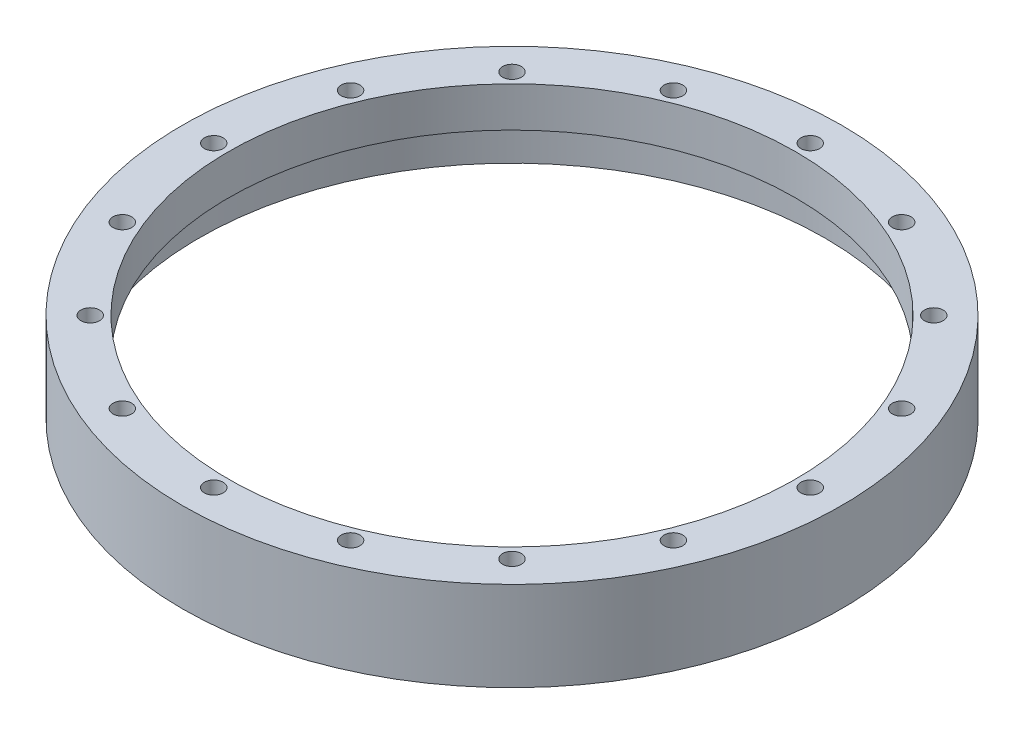
SolidWorks part; units mm, degrees
material "6061-T6 (SS)"
ref_plane "Front Plane" through (0, 0, 0) normal (0, 0, 1) x (1, 0, 0)
ref_plane "Top Plane" through (0, 0, 0) normal (0, 1, 0) x (1, 0, 0)
ref_plane "Right Plane" through (0, 0, 0) normal (1, 0, 0) x (0, 0, -1)
sketch "Sketch1" plane through (0, 0, 0) normal (0, 0, 1) x (1, 0, 0)
  line L0 (-49.4665, 0) -> (-57.4802, 0)
  line L1 (-57.4802, 0) -> (-57.4802, -15.5956)
  line L2 (-57.4802, -15.5956) -> (-54.5719, -15.5956)
  line L3 (-54.5719, -15.5956) -> (-54.5719, -6.985)
  line L4 (-54.5719, -6.985) -> (-49.4665, -6.985)
  line L5 (-49.4665, -6.985) -> (-49.4665, 0)
  line L6 (0, 0) -> (0, 8.0765) construction
  dimension "D1" = 49.4665
  dimension "D2" = 54.5719
  dimension "D3" = 57.4802
  dimension "D4" = 15.5956
  dimension "D5" = 6.985
revolve "Revolve1" add sketch "Sketch1" angle 360 about L6
sketch "Sketch2" plane through (0, 0, 0) normal (0, 1, 0) x (1, 0, 0)
  line L0 (0, 49.4665) -> (0, 52.0192) construction
  circle A0 centre (0, 0) radius 49.4665 construction
  dimension "D1" = 52.0192
hole_wizard "#4 Clearance Hole1" positions "3DSketch1" profile "Sketch3" hole size "#4" standard "Ansi Inch"
sketch3d "3DSketch1"
  point P0 (0, 0, -52.0192)
sketch "Sketch3" plane through (0, 0, -52.0192) normal (1, 0, 0) x (0, 0, 1)
  line L0 (0, 0) -> (0, 11.1406)
  line L1 (0, 11.1406) -> (1.6319, 10.16)
  line L2 (1.6319, 10.16) -> (1.6319, 0)
  line L5 (1.6319, 0) -> (0, 0)
  line L10 (0, 11.1406) -> (-1.632, 10.16) construction
  line L11 (0, -6.35) -> (0, 107.95) construction
  dimension "Hole Dia." = 3.2639
  dimension "Hole Depth" = 10.16
  dimension "Drill Angle" = 118
pattern_circular "CirPattern1" count 16 over 360 about axis through (0, 0, 0) along (0, -1, 0) of "#4 Clearance Hole1"
sketch "Sketch4" plane through (0, 0, 0) normal (0, 1, 0) x (1, 0, 0)
  line L0 (0, 0) -> (8.4341, 56.8581) construction
  line L1 (0, 0) -> (13.9665, 55.7576) construction
  line L3 (0, 0) -> (0, 49.4665) construction
  line L4 (8.4341, 56.8581) -> (7.2582, 48.9311)
  line L5 (13.9665, 55.7576) -> (12.0194, 47.9841)
  arc A0 (7.2582, 48.9311) -> (12.0194, 47.9841) centre (0, 0) cw
  circle A1 centre (0, 0) radius 49.4665 construction
  arc A2 (8.4341, 56.8581) -> (13.9665, 55.7576) centre (0, 0) cw
  circle A3 centre (0, 0) radius 57.4802 construction
  dimension "D1" = 5.625
  dimension "D2" = 8.438
